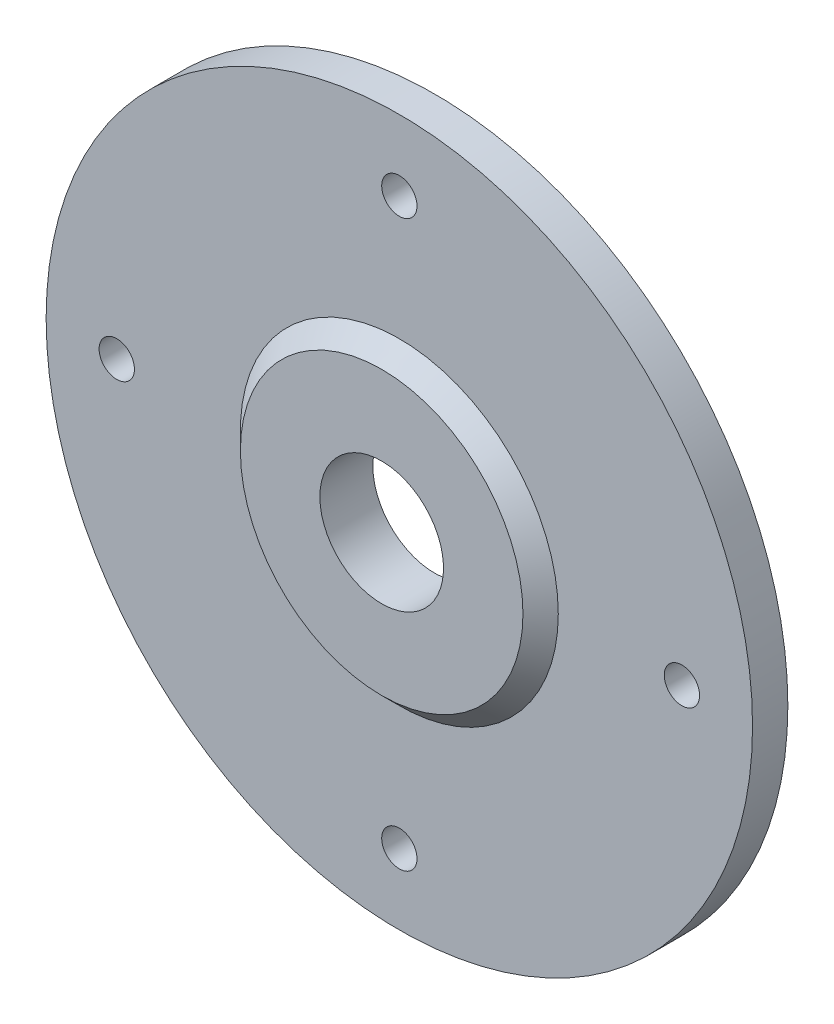
SolidWorks part; units mm, degrees
ref_plane "前视基准面" through (0, 0, 0) normal (0, 0, 1) x (1, 0, 0)
ref_plane "上视基准面" through (0, 0, 0) normal (0, 1, 0) x (1, 0, 0)
ref_plane "右视基准面" through (0, 0, 0) normal (1, 0, 0) x (0, 0, -1)
sketch "草图1" plane through (0, 0, 0) normal (0, 0, 1) x (1, 0, 0)
  circle A0 centre (0, 0) radius 10
  dimension "D1" = 20
extrude "凸台-拉伸1" add sketch "草图1" along normal blind 1
sketch "草图2" plane through (0, 0, 1) normal (0, 0, 1) x (1, 0, 0)
  circle A0 centre (0, 0) radius 4.5
  dimension "D1" = 9
extrude "凸台-拉伸2" add sketch "草图2" along normal blind 0.5
chamfer "倒角1" distance 0.5 1 edges at (4.5, 0, 1.5)
sketch "草图3" plane through (0, 0, 0) normal (0, 0, -1) x (-1, 0, 0)
  circle A0 centre (0, 0) radius 1.75
  dimension "D1" = 3.5
extrude "切除-拉伸1" cut sketch "草图3" against normal through all
sketch "草图4" plane through (0, 0, 0) normal (0, 0, -1) x (-1, 0, 0)
  circle A0 centre (0, 8) radius 0.5
  circle A1 centre (8, 0) radius 0.5
  circle A2 centre (0, -8) radius 0.5
  circle A3 centre (-8, 0) radius 0.5
  point P12 (0, 0)
  dimension "D1" = 1
  dimension "D2" = 8
  dimension "D3" = 4
extrude "切除-拉伸2" cut sketch "草图4" against normal through all
